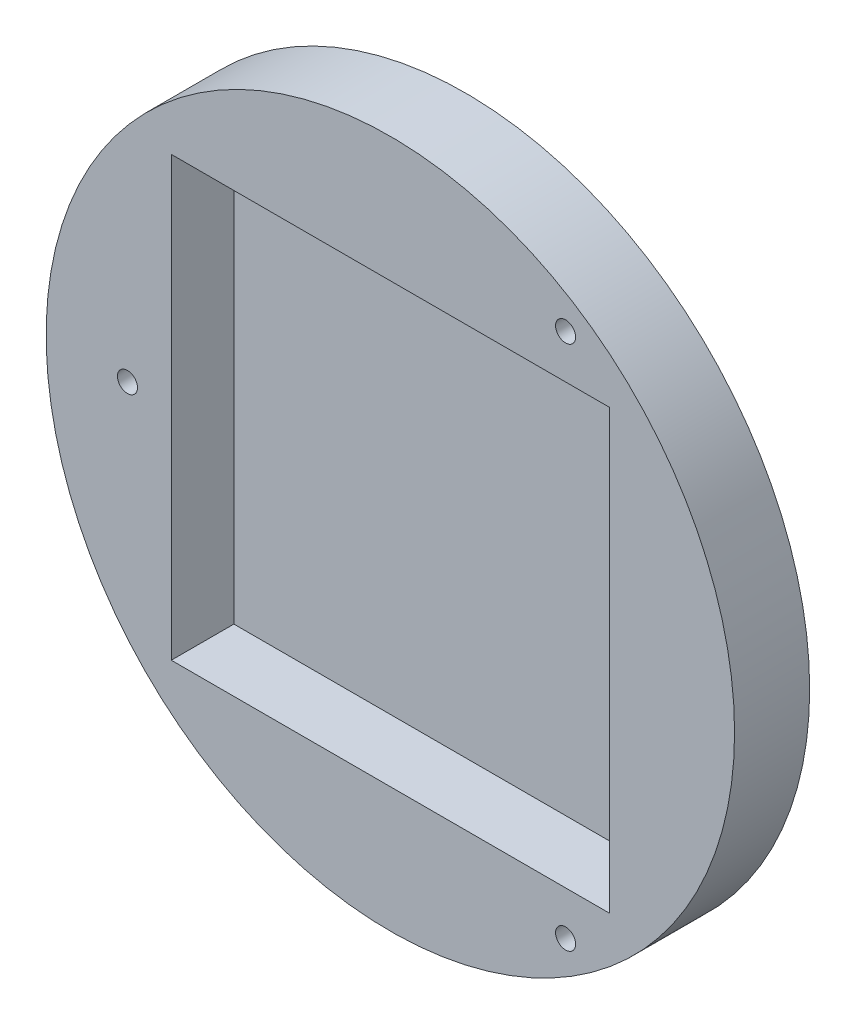
SolidWorks part; units mm, degrees
material "Nylon 101"
ref_plane "Front Plane" through (0, 0, 0) normal (0, 0, 1) x (1, 0, 0)
ref_plane "Top Plane" through (0, 0, 0) normal (0, 1, 0) x (1, 0, 0)
ref_plane "Right Plane" through (0, 0, 0) normal (1, 0, 0) x (0, 0, -1)
sketch "Sketch1" plane through (0, 0, 0) normal (0, 0, 1) x (1, 0, 0)
  line L1 (-18.5, 18.5) -> (18.5, 18.5)
  line L2 (-18.5, 18.5) -> (-18.5, -18.5)
  line L3 (-18.5, -18.5) -> (18.5, -18.5)
  line L4 (18.5, 18.5) -> (18.5, -18.5)
  line L5 (-18.5, 18.5) -> (18.5, -18.5) construction
  line L6 (-18.5, -18.5) -> (18.5, 18.5) construction
  line L7 (-17.5, 17.5) -> (17.5, 17.5)
  line L8 (-17.5, 17.5) -> (-17.5, -17.5)
  line L9 (-17.5, -17.5) -> (17.5, -17.5)
  line L10 (17.5, 17.5) -> (17.5, -17.5)
  line L11 (-17.5, 17.5) -> (17.5, -17.5) construction
  line L12 (-17.5, -17.5) -> (17.5, 17.5) construction
  circle A0 centre (0, 0) radius 27.5
  point P4 (0, 0)
  point P9 (0, 0)
  dimension "D1" = 55
  dimension "D2" = 37
  dimension "D3" = 37
  dimension "D4" = 1
  dimension "D5" = 1
extrude "Boss-Extrude1" add sketch "Sketch1" along normal blind 6 contours A0 L1 L4 L3 L2 | L4 L1 L2 L3 L7 L10 L9 L8 region at (0, 17.9767, 0) region at (-26.7222, 0, 0)
extrude "Boss-Extrude2" add sketch "Sketch1<3>" along normal blind 1 contours L10 L7 L8 L9 region at (0, 0, 0)
sketch "Sketch1<3>" plane through (0, 0, 0) normal (0, 0, 1) x (1, 0, 0) same geometry as "Sketch1"
sketch "Sketch2" plane through (0, 0, 0) normal (0, 1, 0) x (1, 0, 0)
  line L4 (0, 15) -> (0, -15) construction
  line L5 (0, 6.5) -> (0, 0)
  line L6 (0, 0) -> (-6.5, 0)
  arc A1 (0, 6.5) -> (-6.5, 0) centre (0, 0) ccw
  dimension "D1" = 13
  dimension "D4" = 30
revolve "Revolve1" add sketch "Sketch2" angle 360 about L4
hole_wizard "M2x0.4 Tapped Hole1" positions "Sketch3" profile "Sketch4" tap size "M2x0.4" standard "ANSI Metric" end condition through all
sketch "Sketch3" plane through (0, 0, 6) normal (0, 0, 1) x (1, 0, 0)
  line L0 (-17.5, 17.5) -> (-17.5, -17.5) construction
  line L1 (-17.5, -17.5) -> (17.5, -17.5) construction
  line L2 (-17.5, 17.5) -> (17.5, 17.5) construction
  line L3 (17.5, 17.5) -> (17.5, -17.5) construction
  point P0 (-21, 0)
  point P2 (14, -21)
  point P4 (14, 21)
  dimension "D1" = 3.5
  dimension "D2" = 3.5
  dimension "D3" = 3.5
  dimension "D4" = 3.5
sketch "Sketch4" plane through (-21, 0, 6) normal (1, 0, 0) x (0, -1, 0)
  line L0 (0, 0) -> (0, 12.5)
  line L1 (0, 12.5) -> (0.8, 12.5)
  line L2 (0.8, 12.5) -> (0.8, 0)
  line L5 (0.8, 0) -> (0, 0)
  line L11 (0, -6.35) -> (0, 107.95) construction
  dimension "Thru Tap Drill Dia." = 1.6
  dimension "Thru Tap Drill Depth" = 12.5
cosmetic thread "Hole Thread1" parameters "D2"=2
cosmetic thread "Hole Thread2" parameters "D2"=2
cosmetic thread "Hole Thread3" parameters "D2"=2
